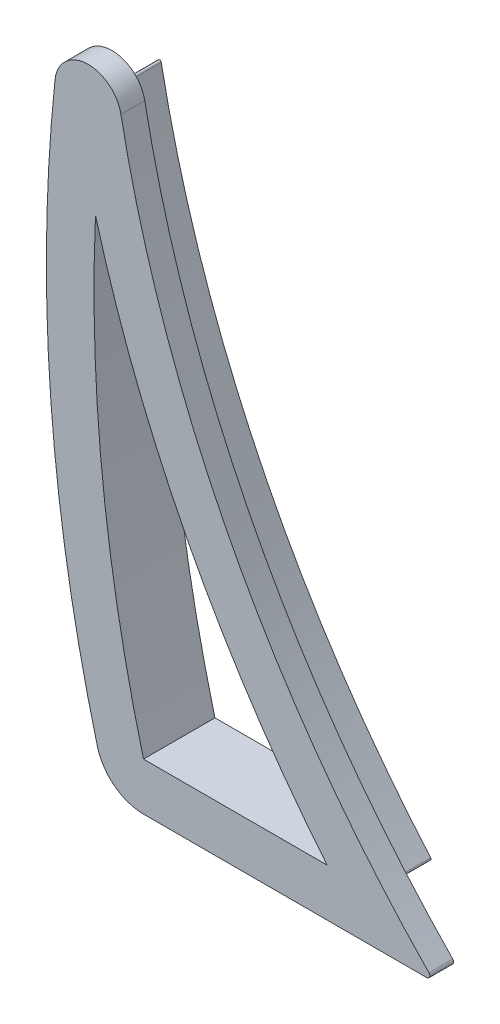
SolidWorks part; units mm, degrees
ref_plane "Plan de face" through (0, 0, 0) normal (0, 0, 1) x (1, 0, 0)
ref_plane "Plan de dessus" through (0, 0, 0) normal (0, 1, 0) x (1, 0, 0)
ref_plane "Plan de droite" through (0, 0, 0) normal (1, 0, 0) x (0, 0, -1)
sketch "Esquisse1" plane through (0, 0, 0) normal (0, 0, 1) x (1, 0, 0)
  line L2 (-4.5246, -18.1471) -> (9.1989, -18.1471)
  line L3 (-4.5246, -17.1471) -> (7.0417, -17.1471)
  arc A6 (-8.0323, 17.5812) -> (9.1989, -18.1471) centre (65.7323, 31.1376) ccw
  arc A7 (-5.4914, -17.4024) -> (-4.5246, -18.1471) centre (-4.5246, -17.1471) ccw
  arc A8 (-8.0323, 17.5812) -> (-5.4914, -17.4024) centre (86.36, 6.8529) ccw
  arc A9 (-7.5489, 10.9915) -> (7.0417, -17.1471) centre (65.7323, 31.1376) ccw
  arc A10 (-7.5489, 10.9915) -> (-4.5246, -17.1471) centre (86.36, 6.8529) ccw
extrude "Boss.-Extru.1" add sketch "Esquisse1" along normal blind 3 contours A6 A8 A7 L2 A10 A9 L3 region at (-4.8911, -17.623, 0)
fillet "Congé1" radius 0.1 1 edges at (-8.0323, 17.5812, 1.5)
sketch "Esquisse2" plane through (0, 0, 3) normal (0, 0, 1) x (1, 0, 0)
  line L0 (-4.5246, -20.1471) -> (13.7815, -20.1471)
  line L1 (-4.5246, -18.1471) -> (9.1989, -18.1471)
  line L2 (-4.5246, -18.1471) -> (9.1989, -18.1471)
  line L3 (-4.5246, -17.1471) -> (7.0417, -17.1471) construction
  line L4 (-4.5246, -17.1471) -> (7.0417, -17.1471)
  arc A0 (-10.0945, 17.1256) -> (-7.4252, -17.9131) centre (86.36, 6.8529) ccw
  arc A1 (-7.4252, -17.9131) -> (-4.5246, -20.1471) centre (-4.5246, -17.1471) ccw
  arc A2 (-5.9444, 17.3012) -> (13.7815, -20.1471) centre (65.7323, 31.1376) ccw
  arc A3 (-5.9444, 17.3012) -> (-10.0945, 17.1256) centre (-8.0064, 16.9032) ccw
  arc A4 (-7.9082, 16.9222) -> (9.1989, -18.1471) centre (65.7323, 31.1376) ccw
  arc A5 (-7.9082, 16.9222) -> (-8.1058, 16.9138) centre (-8.0064, 16.9032) ccw
  arc A6 (-8.1058, 16.9138) -> (-5.4914, -17.4024) centre (86.36, 6.8529) ccw
  arc A7 (-5.4914, -17.4024) -> (-4.5246, -18.1471) centre (-4.5246, -17.1471) ccw
  arc A8 (-7.9082, 16.9222) -> (9.1989, -18.1471) centre (65.7323, 31.1376) ccw
  arc A9 (-7.9082, 16.9222) -> (-8.1058, 16.9138) centre (-8.0064, 16.9032) ccw
  arc A10 (-8.1058, 16.9138) -> (-5.4914, -17.4024) centre (86.36, 6.8529) ccw
  arc A11 (-5.4914, -17.4024) -> (-4.5246, -18.1471) centre (-4.5246, -17.1471) ccw
  arc A12 (-7.5489, 10.9915) -> (-4.5246, -17.1471) centre (86.36, 6.8529) ccw construction
  arc A13 (-7.5489, 10.9915) -> (7.0417, -17.1471) centre (65.7323, 31.1376) ccw construction
  arc A14 (-7.5489, 10.9915) -> (-4.5246, -17.1471) centre (86.36, 6.8529) ccw
  arc A15 (-7.5489, 10.9915) -> (7.0417, -17.1471) centre (65.7323, 31.1376) ccw
  arc M11 (-4.5246, -17.1471) -> (-7.5489, 10.9915) centre (86.36, 6.8529) cw
  arc M12 (-7.5489, 10.9915) -> (7.0417, -17.1471) centre (65.7323, 31.1376) ccw
  line M13 (7.0417, -17.1471) -> (-4.5246, -17.1471)
  dimension "D1" = 0
  dimension "D2" = 2
extrude "Boss.-Extru.2" add sketch "Esquisse2" along normal blind 1.5 contours M11 M13 M12 | A0 A1 L0 A2 A3 region at (-2.5323, -8.1815, 3)
fillet "Congé2" radius 0.2 1 edges at (13.7815, -20.1471, 3.75)
fillet "Congé3" radius 0.1 1 edges at (9.1989, -18.1471, 1.5)
